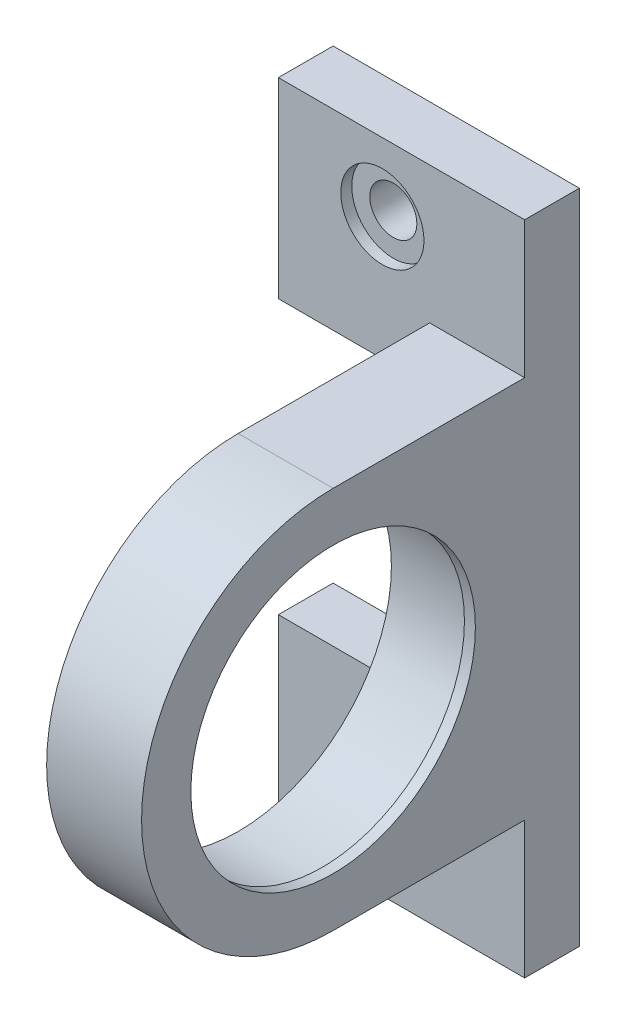
SolidWorks part; units mm, degrees
ref_plane "前视基准面" through (0, 0, 0) normal (0, 0, 1) x (1, 0, 0)
ref_plane "上视基准面" through (0, 0, 0) normal (0, 1, 0) x (1, 0, 0)
ref_plane "右视基准面" through (0, 0, 0) normal (1, 0, 0) x (0, 0, -1)
sketch "草图2" plane through (0, 0, 0) normal (0, 0, 1) x (1, 0, 0)
  line L0 (-14.7736, 24.3382) -> (-14.7736, -35.6618)
  line L1 (-14.7736, -35.6618) -> (30.2264, -35.6618)
  line L2 (7.7264, -35.6618) -> (7.7264, -18.1618)
  line L3 (21.55, -18.1618) -> (-6.0971, -18.1618)
  line L4 (-6.0971, -18.1618) -> (-6.0971, 6.8382)
  line L5 (-6.0971, 6.8382) -> (21.55, 6.8382)
  line L6 (7.7264, 6.8382) -> (7.7264, 24.3382)
  line L7 (30.2264, 24.3382) -> (-14.7736, 24.3382)
  line L8 (7.7264, 28.8603) -> (7.7264, -39.8897) construction
  line L9 (21.55, -18.1618) -> (21.55, 6.8382)
  line L10 (30.2264, 24.3382) -> (30.2264, -35.6618)
  line L11 (-18.1559, -5.6618) -> (33.2411, -5.6618) construction
  line L12 (44.0218, -5.6618) -> (44.0218, 26.2521) construction
  point P16 (-6.0971, -5.6618)
  point P17 (-14.7736, -5.6618)
  dimension "D1" = 45
  dimension "D2" = 25
  dimension "D3" = 60
extrude "凸台-拉伸2" add sketch "草图2" along normal blind 5 contours L6 L7 L0 L1 L2 L3 L4 L5 | L10 L7 L6 L5 L9 L3 L2 L1 region at (-3.5236, 23.6974, 0) region at (18.9764, 23.6974, 0)
sketch "草图4" plane through (0, 0, 5) normal (0, 0, 1) x (1, 0, 0)
  line L0 (-18.165, -5.6618) -> (33.9165, -5.6618) construction
  line L1 (-14.7736, 24.3382) -> (-14.7736, -35.6618) construction
  line L2 (-14.7736, -23.1618) -> (-6.0971, -23.1618)
  line L3 (-14.7736, -23.1618) -> (-14.7736, 11.8382)
  line L4 (-14.7736, 11.8382) -> (-6.0971, 11.8382)
  line L5 (-6.0971, -23.1618) -> (-6.0971, 11.8382)
  line L6 (-6.0971, -18.1618) -> (-6.0971, 6.8382) construction
  line L7 (7.7264, -39.813) -> (7.7264, 28.1228) construction
  line L8 (30.2264, 11.8382) -> (21.55, 11.8382)
  line L9 (21.55, -23.1618) -> (21.55, 11.8382)
  line L10 (30.2264, -23.1618) -> (21.55, -23.1618)
  line L11 (30.2264, -23.1618) -> (30.2264, 11.8382)
  point P17 (-14.7736, -5.6618)
  dimension "D1" = 35
extrude "凸台-拉伸15" add sketch "草图4" along normal blind 35
sketch "草图5" plane through (-14.7736, 0, 0) normal (-1, 0, 0) x (0, 0, 1)
  line L0 (0, -5.6618) -> (40, -5.6618)
  line L1 (0, 24.3382) -> (0, -35.6618) construction
  line L2 (40, 11.8382) -> (40, -23.1618) construction
  line L3 (22.5, 11.8382) -> (40, 11.8382)
  line L4 (40, 11.8382) -> (40, -23.1618)
  line L5 (40, -23.1618) -> (22.5, -23.1618)
  circle A0 centre (22.5, -5.6618) radius 17.5
  line M5 (5, -23.1618) -> (40, -23.1618)
  line M6 (40, -23.1618) -> (40, 11.8382)
  line M7 (40, 11.8382) -> (5, 11.8382)
  dimension "D1" = 35
extrude "切除-拉伸1" cut sketch "草图5" against normal blind 45 contours A0 M5 M6 | A0 M6 M7 region at (-14.7736, 7.9293, 36.0911) region at (-14.7736, -19.2528, 36.0911)
sketch "草图6" plane through (-14.7736, 0, 0) normal (-1, 0, 0) x (0, 0, 1)
  circle A0 centre (22.5, -5.6618) radius 14
  dimension "D1" = 28
extrude "切除-拉伸2" cut sketch "草图6" against normal blind 45
fillet "圆角1" radius 5 4 edges at (-6.0971, 6.8382, 2.5) (21.55, 6.8382, 2.5) (-6.0971, -18.1618, 2.5) (21.55, -18.1618, 2.5)
sketch "草图7" plane through (-6.0971, 0, 0) normal (1, 0, 0) x (0, 0, -1)
  circle A0 centre (-22.5, -5.6618) radius 15
  circle A1 centre (-22.5, -5.6618) radius 13
extrude "凸台-拉伸16" add sketch "草图7" against normal blind 1
sketch "草图8" plane through (21.55, 0, 0) normal (-1, 0, 0) x (0, 0, 1)
  circle A0 centre (22.5, -5.6618) radius 15
  circle A1 centre (22.5, -5.6618) radius 10
sketch "草图9" plane through (0, 0, 5) normal (0, 0, 1) x (1, 0, 0)
  line L0 (7.7264, 24.3382) -> (7.7264, -35.6618)
  line L13 (30.2264, 24.3382) -> (-14.7736, 24.3382) construction
  line L14 (-14.7736, -35.6618) -> (30.2264, -35.6618) construction
sketch "草图11" plane through (0, 0, 5) normal (0, 0, 1) x (1, 0, 0)
  line L0 (-14.7736, 18.0882) -> (30.2264, 18.0882)
  line L1 (-14.7736, 24.3382) -> (-14.7736, 11.8382) construction
  line L2 (30.2264, 24.3382) -> (30.2264, 11.8382) construction
  line L3 (7.7264, 24.3382) -> (7.7264, -35.6618) construction
  line L4 (30.2264, 24.3382) -> (-14.7736, 24.3382) construction
  line L5 (-14.7736, -35.6618) -> (30.2264, -35.6618) construction
  line L6 (7.7264, -5.6618) -> (45.6912, -5.6618) construction
  line L10 (-14.7736, -29.4118) -> (30.2264, -29.4118)
  line L11 (-14.7736, -23.1618) -> (-14.7736, -35.6618) construction
  point P4 (-1.7736, 18.0882)
  point P16 (-1.7736, -29.4118)
  point P18 (17.2264, -29.4118)
  point P25 (17.2264, 18.0882)
  dimension "D1" = 13
split "分割1" trim tools "草图9" bodies to split 111 resulting bodies 117 118
delete or keep bodies "实体-删除/保留 2" type delete bodies bodies 117
hole_wizard "打孔尺寸(%根据六角头螺)栓 全螺纹的类型1" positions "3D草图2" profile "草图13" counterbore size "M4" standard "GB"
sketch3d "3D草图2"
  point P0 (17.2264, 18.0882, 5)
  point P3 (17.2264, -29.4118, 5)
sketch "草图13" plane through (17.2264, 18.0882, 5) normal (1, 0, 0) x (0, -1, 0)
  line L0 (0, 0) -> (0, 6.2919)
  line L1 (0, 6.2919) -> (2.15, 5)
  line L2 (2.15, 5) -> (2.15, 1)
  line L3 (2.15, 1) -> (3.8, 1)
  line L4 (3.8, 1) -> (3.8, 0)
  line L5 (3.8, 0) -> (0, 0)
  line L10 (0, 6.2919) -> (-2.15, 5) construction
  line L11 (0, -6.35) -> (0, 107.95) construction
  dimension "孔直径" = 4.3
  dimension "孔深度" = 5
  dimension "柱形沉头孔直径" = 7.6
  dimension "柱形沉头孔深度" = 1
  dimension "导头角度" = 118
ref_plane "基准面1" through (30.2264, 0, 0) normal (1, 0, 0) x (0, 0, -1)
sketch "草图14" plane through (30.2264, 0, 0) normal (1, 0, 0) x (0, 0, -1)
  circle A1 centre (-22.5, -5.6618) radius 14 construction
  circle A3 centre (-22.5, -5.6618) radius 14
extrude "拉伸-薄壁1" add sketch "草图14" against normal blind 1 thin thin type one direction reverse wall 1
